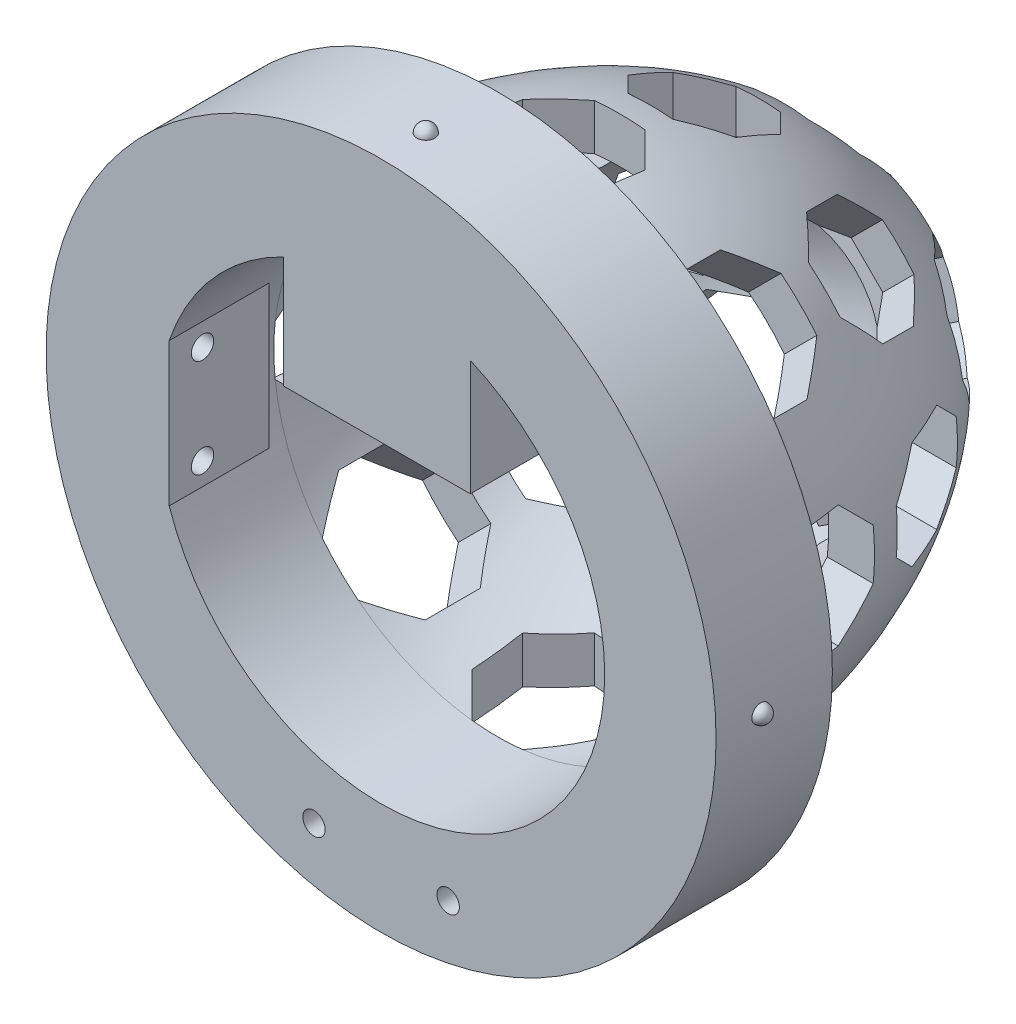
SolidWorks part; units mm, degrees
ref_plane "Front Plane" through (0, 0, 0) normal (0, 0, 1) x (1, 0, 0)
ref_plane "Top Plane" through (0, 0, 0) normal (0, 1, 0) x (1, 0, 0)
ref_plane "Right Plane" through (0, 0, 0) normal (1, 0, 0) x (0, 0, -1)
sketch "Croquis1" plane through (0, 0, 0) normal (0, 1, 0) x (1, 0, 0)
  line L0 (0, 38.5) -> (0, 43.5)
  line L2 (25, 0) -> (25, -13)
  line L3 (25, -13) -> (37.45, -13)
  line L4 (37.45, -13) -> (37.45, 0)
  line L5 (37.45, 0) -> (30, 0)
  ellipse E0 centre (0, 0) end of major axis (0, -43.5) minor radius 30 (30, 0) -> (0, 43.5) ccw
  ellipse E1 centre (0, 0) end of major axis (0, 38.5) minor radius 25 (25, 0) -> (0, 38.5) ccw
  dimension "D1" = 5
  dimension "D2" = 5
  dimension "D3" = 43.5
  dimension "D4" = 30
  dimension "D5" = 7.45
  dimension "D6" = 13
revolve "Revolución1" add sketch "Croquis1" angle 360 about L0
sketch "Croquis2" plane through (0, 0, 13) normal (0, 0, 1) x (1, 0, 0)
  line L1 (-7.5, -24.8572) -> (7.5, -24.8572) construction
  line L2 (-7.5, -24.8572) -> (-7.5, -30.6303) construction
  line L3 (-7.5, -30.6303) -> (7.5, -30.6303) construction
  line L4 (7.5, -24.8572) -> (7.5, -30.6303) construction
  circle A0 centre (-7.5, -30.6303) radius 1.25
  circle A1 centre (7.5, -30.6303) radius 1.25
  point P4 (0, -24.8572)
  dimension "D2" = 2.5
  dimension "D1" = 15
extrude "Cortar-Extruir1" cut sketch "Croquis2" against normal blind 10
sketch "Croquis3" plane through (0, 0, 0) normal (1, 0, 0) x (0, 0, -1)
  line L0 (-13, 25) -> (-13, -25) construction
  line L1 (-9.271, 5.5) -> (-3.5212, 5.5) construction
  line L2 (-9.271, 5.5) -> (-9.271, -5.5) construction
  line L3 (-9.271, -5.5) -> (-3.5212, -5.5) construction
  line L4 (-3.5212, 5.5) -> (-3.5212, -5.5) construction
  line L5 (-13, 8) -> (-1.8369, 8)
  line L6 (-13, 8) -> (-13, -8)
  line L7 (-13, -8) -> (-1.8369, -8)
  line L8 (-1.8369, 8) -> (-1.8369, -8)
  circle A0 centre (-9.271, 5.5) radius 1.25
  circle A1 centre (-9.271, -5.5) radius 1.25
  point P6 (-3.5212, 0)
  dimension "D1" = 2.5
  dimension "D2" = 11
  dimension "D3" = 16
  dimension "D4" = 2.5
extrude "Saliente-Extruir1" add sketch "Croquis3" against normal up to surface (23.6854 mm away) contours L6 L5 L8 L7 | A0 | A1 up to face at (25, 0, 13)
sketch "Croquis4" plane through (0, 0, 0) normal (1, 0, 0) x (0, 0, -1)
  line L1 (-13, 8) -> (-1.8369, 8)
  line L2 (-13, 8) -> (-13, -8)
  line L3 (-13, -8) -> (-1.8369, -8)
  line L4 (-1.8369, 8) -> (-1.8369, -8)
extrude "Cortar-Extruir2" cut sketch "Croquis4" against normal up to vertex (23.6854 mm away) up to point (-23.6854, 8, 13)
sketch "Croquis5" plane through (-23.6854, 0, 0) normal (1, 0, 0) x (0, 0, -1)
  circle A0 centre (-9.271, 5.5) radius 1.25
  circle A1 centre (-9.271, -5.5) radius 1.25
extrude "Cortar-Extruir3" cut sketch "Croquis5" against normal blind 10
sketch "Croquis6" plane through (0, 0, 0) normal (0, 1, 0) x (1, 0, 0)
  line L0 (-23.6854, -13) -> (25, -13) construction
  line L1 (-7.05, -10) -> (7.05, -10)
  line L2 (-7.05, -10) -> (-7.05, 5)
  line L3 (-7.05, 5) -> (7.05, 5)
  line L4 (7.05, -10) -> (7.05, 5)
  line L5 (-10.9173, -13) -> (9.9768, -13)
  line L6 (-10.9173, -13) -> (-10.9173, 8.4415)
  line L7 (-10.9173, 8.4415) -> (9.9768, 8.4415)
  line L8 (9.9768, -13) -> (9.9768, 8.4415)
  point P4 (0, -10)
  point P12 (10.4609, 4.4)
  point P13 (11.9936, 16.186)
  point P14 (9.9768, 8.4415)
  dimension "D1" = 14.1
  dimension "D3" = 3
  dimension "D4" = 15
extrude "Saliente-Extruir2" add sketch "Croquis6" along normal up to surface (23.9854 mm away) up to face at (25, 0, 0)
sketch "Croquis7" plane through (0, 0, 0) normal (0, -1, 0) x (1, 0, 0)
  line L0 (-10.9173, -8.4415) -> (9.9768, -8.4415) construction
  line L1 (-10.9173, 13) -> (9.9768, 13)
  line L2 (-10.9173, 13) -> (-10.9173, -8.4415)
  line L3 (-10.9173, -8.4415) -> (9.9768, -8.4415)
  line L4 (9.9768, 13) -> (9.9768, -8.4415)
extrude "Cortar-Extruir4" cut sketch "Croquis7" against normal blind 10
sketch "Croquis8" plane through (0, 10, 0) normal (0, -1, 0) x (1, 0, 0)
  line L0 (-10.9173, -8.4415) -> (9.9768, -8.4415) construction
  line L1 (-2.7058, -8.4415) -> (-7.05, -8.4415)
  line L2 (-2.7058, -8.4415) -> (-2.7058, -5)
  line L3 (-2.7058, -5) -> (-7.05, -5)
  line L4 (-7.05, -8.4415) -> (-7.05, -5)
  point P7 (-2.7058, -8.4415)
extrude "Cortar-Extruir5" cut sketch "Croquis8" against normal blind 5
sketch "Croquis11" plane through (-23.6854, 0, 0) normal (1, 0, 0) x (0, 0, -1)
  line L0 (4.0045, 6.8362) -> (0, 2.8316)
  line L1 (0, -25) -> (0, 22.923) construction
  line L2 (0, 2.8316) -> (0, -2.8316)
  line L3 (0, -2.8316) -> (4.0045, -6.8362)
  line L4 (4.0045, -6.8362) -> (9.6678, -6.8362)
  line L5 (9.6678, -6.8362) -> (13.6724, -2.8316)
  line L6 (13.6724, -2.8316) -> (13.6724, 2.8316)
  line L7 (13.6724, 2.8316) -> (9.6678, 6.8362)
  line L8 (9.6678, 6.8362) -> (4.0045, 6.8362)
  line L9 (20.6492, 6.0243) -> (17.1203, 2.4953)
  line L10 (17.1203, 2.4953) -> (17.1203, -2.4953)
  line L11 (17.1203, -2.4953) -> (20.6492, -6.0243)
  line L12 (20.6492, -6.0243) -> (25.6399, -6.0243)
  line L13 (25.6399, -6.0243) -> (29.1689, -2.4953)
  line L14 (29.1689, -2.4953) -> (29.1689, 2.4953)
  line L15 (29.1689, 2.4953) -> (25.6399, 6.0243)
  line L16 (25.6399, 6.0243) -> (20.6492, 6.0243)
  line L17 (-1.8369, 0) -> (0, 0) construction
  line L18 (-1.8369, -8) -> (-1.8369, 8) construction
  line L19 (13.6724, 0) -> (17.1203, 0) construction
  point P12 (17.1209, 2.445)
  dimension "D1" = 135
extrude "Cortar-Extruir6" cut sketch "Croquis11" against normal mid plane 13 contours L9 L10 L11 L12 L13 L14 L15 L16 | L8 L0 L2 L3 L4 L5 L6 L7
sketch "Croquis12" plane through (0, 0, 0) normal (0, 1, 0) x (1, 0, 0)
  line L0 (0, 0) -> (0, 58.9364) construction
pattern_circular "MatrizC1" count 8 every 45 about axis through (0, 0, 0) along (0, 0, -1) of "Cortar-Extruir6"
sketch "Croquis14" plane through (0, 8.252, -8.252) normal (0, -0.7071, 0.7071) x (1, 0, 0)
  line L0 (2.8212, -8.3724) -> (-2.8212, -8.3724)
  line L1 (-2.8212, -8.3724) -> (-6.2993, -11.8504)
  line L2 (-6.2993, -11.8504) -> (-6.2993, -17.2677)
  line L3 (-6.2993, -17.2677) -> (-2.8212, -20.7458)
  line L4 (-2.8212, -20.7458) -> (2.8212, -20.7458)
  line L5 (2.8212, -20.7458) -> (6.2993, -17.2677)
  line L6 (6.2993, -17.2677) -> (6.2993, -11.8504)
  line L7 (6.2993, -11.8504) -> (2.8212, -8.3724)
  ellipse E0 centre (0, 9.1924) end of major axis (25, 9.1924) minor radius 17.6777 (-23.6854, 3.5355) -> (9.9768, 25.4014) ccw construction
  point P2 (0, 0)
  point P9 (0, 0)
  point P10 (-5.1006, -14.4886)
  point P11 (0, -8.3724)
  point P13 (2.685, -16.0874)
  point P14 (0, 0)
  point P15 (2.824, -19.146)
  point P16 (2.7728, -6.7725)
  point P17 (2.8212, -8.3724)
extrude "Cortar-Extruir7" cut sketch "Croquis14" against normal blind 37
pattern_circular "MatrizC2" count 5 every 72 about axis through (0, 0, 0) along (0, 0, -1) of "Cortar-Extruir7"
sketch "Croquis16" plane through (0, 0, 0) normal (1, 0, 0) x (0, 0, -1)
  line L0 (-9, 37.45) -> (-7, 37.45)
  line L1 (0, -37.45) -> (0, 37.45) construction
  arc A0 (-7, 37.45) -> (-9, 37.45) centre (-8, 37.45) ccw
  dimension "D1" = 1
  dimension "D2" = 8
revolve "Revolución2" add sketch "Croquis16" angle 360 about L0
pattern_circular "MatrizC3" count 4 every 90 about axis through (0, 0, 0) along (0, 0, -1) of "Revolución2"
